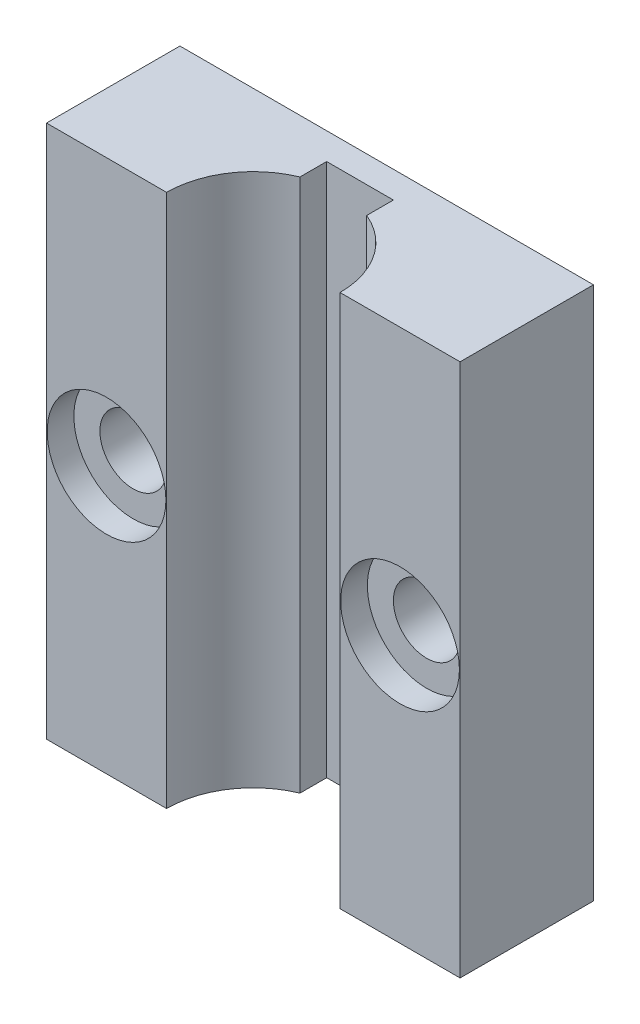
SolidWorks part; units mm, degrees
ref_plane "Front" through (0, 0, 0) normal (0, 0, 1) x (1, 0, 0)
ref_plane "Top" through (0, 0, 0) normal (0, 1, 0) x (1, 0, 0)
ref_plane "Right" through (0, 0, 0) normal (1, 0, 0) x (0, 0, -1)
other "Configuration Table"
sketch "Sketch1" plane through (0, 0, 0) normal (0, 0, 1) x (1, 0, 0)
  line L1 (-24.6545, 23.5781) -> (6.3455, 23.5781)
  line L2 (-24.6545, 23.5781) -> (-24.6545, -16.4219)
  line L3 (-24.6545, -16.4219) -> (6.3455, -16.4219)
  line L4 (6.3455, 23.5781) -> (6.3455, -16.4219)
  dimension "D1" = 40
  dimension "D2" = 31
extrude "Boss-Extrude1" add sketch "Sketch1" along normal blind 10 contours L1 L4 L3 L2
sketch "Sketch2" plane through (0, 23.5781, 0) normal (0, 1, 0) x (1, 0, 0)
  line L0 (-9.1545, 0) -> (-9.1545, -10) construction
  line L1 (-24.6545, 0) -> (6.3455, 0) construction
  line L2 (-24.6545, -10) -> (6.3455, -10) construction
  circle A0 centre (-9.1545, -10) radius 6.5
  dimension "D1" = 13
extrude "Cut-Extrude1" cut sketch "Sketch2" against normal through all
sketch "Sketch3" plane through (0, 0, 10) normal (0, 0, 1) x (1, 0, 0)
  line L0 (-24.6545, 3.5781) -> (-15.6545, 3.5781) construction
  line L1 (-24.6545, 23.5781) -> (-24.6545, -16.4219) construction
  line L2 (-15.6545, 23.5781) -> (-15.6545, -16.4219) construction
  line L3 (-15.6545, 3.5781) -> (6.3455, 3.5781) construction
  line L4 (6.3455, 23.5781) -> (6.3455, -16.4219) construction
  line L5 (-2.6545, 3.5781) -> (6.3455, 3.5781) construction
  line L6 (-2.6545, -16.4219) -> (-2.6545, 23.5781) construction
  circle A0 centre (-20.1545, 3.5781) radius 2.5
  circle A1 centre (1.8455, 3.5781) radius 2.5
  circle A2 centre (-20.1545, 3.5781) radius 4.45
  circle A3 centre (1.8455, 3.5781) radius 4.45
  dimension "D1" = 5
  dimension "D2" = 5
  dimension "D3" = 8.9
  dimension "D4" = 8.9
extrude "Cut-Extrude2" cut sketch "Sketch3" against normal through all contours A0 | A1 region at (-20.1545, 3.5781, 10) region at (1.8455, 3.5781, 10)
extrude "Cut-Extrude5" cut sketch "Sketch3<4>" against normal blind 2
sketch "Sketch3<4>" plane through (0, 0, 10) normal (0, 0, 1) x (1, 0, 0) same geometry as "Sketch3"
sketch "Sketch4" plane through (0, 23.5781, 0) normal (0, 1, 0) x (1, 0, 0)
  line L0 (6.3455, -3.5) -> (-24.6545, -3.5) construction
  line L1 (6.3455, -10) -> (6.3455, 0) construction
  line L2 (-24.6545, -10) -> (-24.6545, 0) construction
  line L3 (-9.1545, 0) -> (-9.1545, -3.5) construction
  line L4 (-24.6545, 0) -> (6.3455, 0) construction
  line L5 (-9.1545, -2) -> (-9.1545, -5) construction
  line L6 (-11.6545, -2) -> (-6.6545, -2)
  line L7 (-11.6545, -2) -> (-11.6545, -5)
  line L8 (-11.6545, -5) -> (-6.6545, -5)
  line L9 (-6.6545, -2) -> (-6.6545, -5)
  line L10 (-11.6545, -3.5) -> (-6.6545, -3.5) construction
  arc A0 (-2.6545, -10) -> (-15.6545, -10) centre (-9.1545, -10) ccw construction
  point P18 (-9.1545, -3.5)
  dimension "D1" = 3
  dimension "D2" = 5
  dimension "D3" = 0
extrude "Cut-Extrude6" cut sketch "Sketch4" against normal through all
